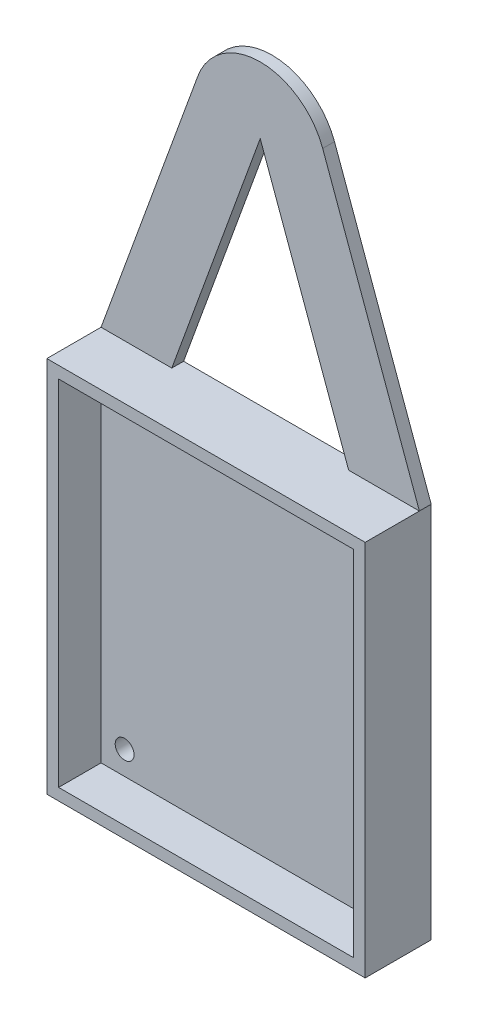
SolidWorks part; units mm, degrees
ref_plane "Front Plane" through (0, 0, 0) normal (0, 0, 1) x (1, 0, 0)
ref_plane "Top Plane" through (0, 0, 0) normal (0, 1, 0) x (1, 0, 0)
ref_plane "Right Plane" through (0, 0, 0) normal (1, 0, 0) x (0, 0, -1)
sketch "Sketch1" plane through (0, 0, 0) normal (0, 0, 1) x (1, 0, 0)
  line L0 (-37.5, 80) -> (37.5, 80)
  line L2 (-67.5, 80) -> (-67.5, -80)
  line L3 (-67.5, -80) -> (67.5, -80)
  line L4 (67.5, 80) -> (67.5, -80)
  line L5 (-67.5, 80) -> (67.5, -80) construction
  line L6 (-67.5, -80) -> (67.5, 80) construction
  line L7 (-37.5, 80) -> (0, 183.0304)
  line L8 (0, 183.0304) -> (37.5, 80)
  line L9 (26.4907, 192.6722) -> (67.5, 80)
  line L11 (-67.5, 80) -> (-26.4907, 192.6722)
  arc A0 (-26.4907, 192.6722) -> (26.4907, 192.6722) centre (0, 183.0304) cw
  point P0 (0, 0)
  dimension "D5" = 70
  dimension "D1" = 135
  dimension "D2" = 160
  dimension "D3" = 30
  dimension "D4" = 30
  dimension "D6" = 70
  dimension "D7" = 70
  dimension "D8" = 70
  dimension "D9" = 160
extrude "Boss-Extrude1" add sketch "Sketch1" along normal blind 5
sketch "Sketch2" plane through (0, 0, 5) normal (0, 0, 1) x (1, 0, 0)
  line L0 (-67.5, 80) -> (67.5, 80)
  line L1 (67.5, 80) -> (67.5, -80)
  line L2 (67.5, -80) -> (-67.5, -80)
  line L3 (-67.5, -80) -> (-67.5, 80)
  line L4 (-37.5, 80) -> (37.5, 80) construction
  line L9 (-62.5, 75) -> (62.5, -75) construction
  line L10 (-62.5, -75) -> (62.5, 75) construction
  line L13 (67.5, -80) -> (67.5, 80) construction
  line L14 (-67.5, 80) -> (-67.5, -80) construction
  point P4 (0, 0)
extrude "Boss-Extrude2" add sketch "Sketch2" along normal blind 5
sketch "Sketch3" plane through (0, 0, 5) normal (0, 0, 1) x (1, 0, 0)
  line L0 (-112.7804, 0) -> (141.2682, 0) construction
  line L1 (0, 110.8789) -> (0, -99.0722) construction
  line L2 (-67.5, 80) -> (-67.5, -80) construction
  line L3 (67.5, 80) -> (-67.5, 80) construction
  circle A0 centre (-52.5, 65) radius 4
  circle A1 centre (52.5, 65) radius 4
  circle A2 centre (52.5, -65) radius 4
  circle A3 centre (-52.5, -65) radius 4
  dimension "D1" = 8
  dimension "D2" = 15
  dimension "D3" = 15
extrude "Cut-Extrude1" cut sketch "Sketch3" against normal blind 1 and the other way blind 5
sketch "Sketch4" plane through (0, 0, 10) normal (0, 0, 1) x (1, 0, 0)
  line L1 (-67.5, 80) -> (67.5, 80)
  line L2 (-67.5, 80) -> (-67.5, -80)
  line L3 (-67.5, -80) -> (67.5, -80)
  line L4 (67.5, 80) -> (67.5, -80)
  line L5 (-67.5, 80) -> (67.5, -80) construction
  line L6 (-67.5, -80) -> (67.5, 80) construction
  line L11 (-63.2812, 75) -> (63.2812, -75) construction
  line L12 (-63.2812, -75) -> (63.2812, 75) construction
  line L13 (-62.5, 75) -> (62.5, 75)
  line L14 (-62.5, 75) -> (-62.5, -75)
  line L15 (-62.5, -75) -> (62.5, -75)
  line L16 (62.5, 75) -> (62.5, -75)
  line L17 (-62.5, 75) -> (62.5, -75) construction
  line L18 (-62.5, -75) -> (62.5, 75) construction
  point P0 (0, 0)
  point P7 (0, 0)
  point P12 (0, 0)
  dimension "D1" = 5
  dimension "D2" = 5
extrude "Boss-Extrude3" add sketch "Sketch4" along normal blind 18
sketch "Sketch5" plane through (0, 0, 0) normal (0, 0, -1) x (-1, 0, 0)
  line L0 (-141.6585, 0) -> (175.9999, 0) construction
  line L1 (0, 101.9033) -> (0, -99.0722) construction
  line L2 (37.5, 80) -> (-37.5, 80) construction
  line L3 (-67.5, -80) -> (-67.5, 80) construction
  circle A0 centre (-52.5, 65) radius 4
  circle A1 centre (52.5, 65) radius 4
  circle A2 centre (52.5, -65) radius 4
  circle A3 centre (-52.5, -65) radius 4
  dimension "D1" = 8
  dimension "D2" = 15
  dimension "D3" = 15
extrude "Cut-Extrude2" cut sketch "Sketch5" against normal blind 2
hole_wizard "Ø2.5mm Dowel Hole1" positions "Sketch6" profile "Sketch7" hole size "Ø2.5" standard "ISO"
sketch "Sketch6" plane through (0, 0, 2) normal (0, 0, -1) x (-1, 0, 0)
  point P0 (-52.5, 65)
  point P3 (52.5, 65)
  point P6 (52.5, -65)
  point P9 (-52.5, -65)
sketch "Sketch7" plane through (52.5, 65, 2) normal (1, 0, 0) x (0, 1, 0)
  line L0 (0, 0) -> (0, 12.7511)
  line L1 (0, 12.7511) -> (1.25, 12)
  line L2 (1.25, 12) -> (1.25, 0)
  line L5 (1.25, 0) -> (0, 0)
  line L10 (0, 12.7511) -> (-1.25, 12) construction
  line L11 (0, -6.35) -> (0, 107.95) construction
  dimension "Hole Dia." = 2.5
  dimension "Hole Depth" = 12
  dimension "Drill Angle" = 118
